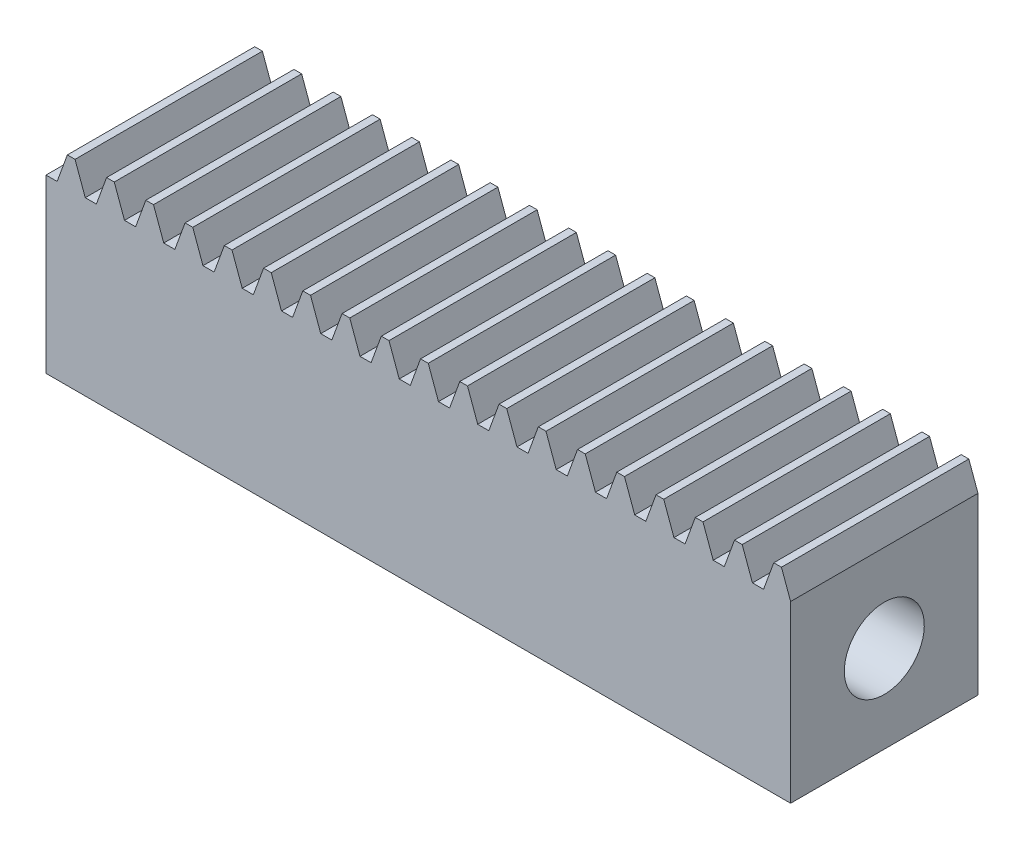
SolidWorks part; units mm, degrees
extrude "Blank" add sketch "BlankSke" against normal blind 15
sketch "BlankSke" plane through (0, 0, 0) normal (0, 0, 1) x (1, 0, 0)
  line L1 (0, 0) -> (100, 0)
  line L2 (0, 0) -> (0, 16)
  line L3 (0, 16) -> (100, 16)
  line L4 (100, 0) -> (100, 16)
  dimension "Length" = 100
ref_plane "Plane1" through (0, 0, 0) normal (0, 0, 1) x (1, 0, 0)
ref_plane "Plane2" through (0, 0, 0) normal (0, 1, 0) x (1, 0, 0)
ref_plane "Plane3" through (0, 0, 0) normal (1, 0, 0) x (0, 0, -1)
sketch "HoldingSke" plane through (0, 0, 0) normal (0, 1, 0) x (1, 0, 0)
  line L0 (0, 0) -> (0.1392, 0.9903)
  line L1 (-15, 0) -> (100, 0) construction
  line L2 (0, 0) -> (-2.1039, 2.3779)
  line L3 (0, 0) -> (-11.863, 4.5341)
  line L4 (0, 0) -> (7.2428, 4.7035)
  line L5 (0, 0) -> (-23.7986, -8.8762)
  line L6 (0, 0) -> (-10.5278, -7.1032)
  line L9 (-71.009, 38.7566) -> (22.9603, 72.9586)
  line L10 (-76.2, 3.3779) -> (-61.2, 3.3779)
  line L11 (0, 0) -> (-15, 0)
  line L12 (-76.2, 101.6) -> (-76.162, 101.6)
  line L13 (24.9733, 27.94) -> (52.9518, 28.4284)
  line L14 (24.9733, 27.94) -> (24.9743, 27.94)
  line L15 (24.9733, 27.94) -> (100.4006, 29.5858)
  circle A0 centre (0, 0) radius 19.05
  circle A1 centre (0, 0) radius 7.5
  circle A2 centre (0, 0) radius 12.7
  dimension "Num_teeth" = 33
  dimension "Width" = 15
  dimension "Length" = 100
  dimension "Pitch_height" = 15
sketch "TooCutSkeIll" plane through (0, 0, 0) normal (0, 0, 1) x (1, 0, 0)
  line L0 (-1.2538, 15.9737) -> (-0.5045, 13.9152)
  line L1 (-0.2687, 13.75) -> (0.2687, 13.75)
  line L2 (0.5045, 13.9152) -> (1.2538, 15.9737)
  line L3 (100, 16) -> (0, 16) construction
  line L4 (0, 0) -> (0, 64.897) construction
  line L5 (-13.208, 15) -> (12.954, 15) construction
  line L6 (0, 0) -> (100, 0) construction
  line L7 (0.8994, 15) -> (0.8994, 48.7463) construction
  line L8 (-0.8994, 15) -> (-0.8994, 48.7463) construction
  line L9 (1.2914, 16) -> (1.2914, 16.0254)
  line L10 (-1.2914, 16) -> (-1.2914, 16.0254)
  line L11 (-1.2914, 16.0254) -> (1.2914, 16.0254)
  arc A0 (0.2687, 13.75) -> (0.5045, 13.9152) centre (0.2687, 14.001) ccw
  arc A1 (-0.5045, 13.9152) -> (-0.2687, 13.75) centre (-0.2687, 14.001) ccw
  arc A2 (1.2914, 16) -> (1.2538, 15.9737) centre (1.2914, 15.96) ccw
  arc A3 (-1.2538, 15.9737) -> (-1.2914, 16) centre (-1.2914, 15.96) ccw
  dimension "Addendum_plus" = 1.0254
  dimension "Pitch_height" = 15
  dimension "Pressure_angle" = 20
  dimension "Gap_width" = 1.7988
  dimension "Dedendum" = 1.25
extrude "ToothCutIll" [suppressed] cut sketch "TooCutSkeIll" against normal through all
sketch "TooCutSkeSim" plane through (0, 0, 0) normal (0, 0, 1) x (1, 0, 0)
  line L0 (0.4444, 13.75) -> (-0.4444, 13.75)
  line L1 (1.2726, 16.0254) -> (0.4444, 13.75)
  line L2 (0, 17.4625) -> (0, 53.467) construction
  line L3 (1.2726, 16.0254) -> (-1.2726, 16.0254)
  line L6 (-1.2726, 16.0254) -> (-0.4444, 13.75)
  line L9 (-0.8994, 15) -> (0.8994, 15) construction
  line L10 (0, 0) -> (100, 0) construction
  line L11 (0.8994, 15) -> (0.8994, 53.467) construction
  line L12 (-0.8994, 15) -> (-0.8994, 53.467) construction
  dimension "Addendum_plus" = 1.0254
  dimension "Pitch_height" = 15
  dimension "Pressure_angle" = 20
  dimension "Gap_width" = 1.7988
  dimension "Dedendum" = 1.25
extrude "ToothCutSim" cut sketch "TooCutSkeSim" against normal through all
pattern_linear "TeethCuts" count 33 spacing 3.1416 along (1, 0, 0) of "ToothCutIll", "ToothCutSim"
sketch "Sketch1" plane through (100, 0, 0) normal (1, 0, 0) x (0, 0, -1)
  line L0 (0, 13.9877) -> (15, 0) construction
  circle A0 centre (7.5, 6.9939) radius 3.2
  dimension "D1" = 6.4
extrude "Cut-Extrude1" cut sketch "Sketch1" against normal blind 50
sketch "Sketch2" plane through (0, 0, 0) normal (0, 0, 1) x (1, 0, 0)
  line L1 (0, 0) -> (40.3963, 0)
  line L2 (0, 0) -> (0, 26.2501)
  line L3 (0, 26.2501) -> (40.3963, 26.2501)
  line L4 (40.3963, 0) -> (40.3963, 26.2501)
extrude "Cut-Extrude2" cut sketch "Sketch2" against normal through all
fillet "Fillet1" [suppressed] radius 8
equation "' \"Module@HoldingSke\" = 6.35"
equation "' \"Num_teeth@HoldingSke\" = 12"
equation "' \"Ap@HoldingSke\" =  20"
equation "' \"Ap@HoldingSke\" = 20"
equation "' \"Width@HoldingSke\" = 0.25 * 25.4"
equation "' \"Show_teeth@HoldingSke\" = 500"
equation "' \"Backlash@HoldingSke\" = 0.009 * 25.4"
equation "' \"Addendum_fac@HoldingSke\" = 1.0"
equation "' \"Dedendum_fac@HoldingSke\" = 1.25"
equation "' \"Dedendum_add@HoldingSke\" = 0.00005 * 25.4"
equation "' \"Clearance_fac@HoldingSke\" = 0.25"
equation "' \"Pitch_height@HoldingSke\" = 1 * 25.4"
equation "' \"Length@HoldingSke\" = 4.71 * 25.4"
equation "\"Pitch@HoldingSke\" = 1 / \"Module@HoldingSke\""
equation "\"MPH@HoldingSke\" = \"Dedendum_fac@HoldingSke\" / \"Pitch@HoldingSke\" + 2 * \"Dedendum_add@HoldingSke\" + 0.002 * 25.4"
equation "\"MPH@HoldingSke\" = ((sgn( \"MPH@HoldingSke\" - \"Pitch_height@HoldingSke\")+1)*( \"MPH@HoldingSke\" - \"Pitch_height@HoldingSke\"))/2 + \"Pitch_height@HoldingSke\""
equation "\"Blank_height@BlankSke\" = \"Pitch_height@HoldingSke\" + \"Addendum_fac@HoldingSke\"  / \"Pitch@HoldingSke\" "
equation "\"Length@BlankSke\" =  \"Length@HoldingSke\""
equation "\"Face_width@Blank\" = \"Width@HoldingSke\""
equation "\"Pressure_angle@TooCutSkeIll\" = \"Ap@HoldingSke\""
equation "\"Addendum_plus@TooCutSkeIll\" =  \"Addendum_fac@HoldingSke\"  / \"Pitch@HoldingSke\" + 0.001 *25.4"
equation "\"Dedendum@TooCutSkeIll\" = \"Dedendum_fac@HoldingSke\"  / \"Pitch@HoldingSke\""
equation "\"Pitch_height@TooCutSkeIll\" =  \"MPH@HoldingSke\""
equation "\"Gap_width@TooCutSkeIll\" = 3.14159265 / 2 / \"Pitch@HoldingSke\" + 6 * \"Backlash@HoldingSke\""
equation "\"Pressure_angle@TooCutSkeSim\" = \"Ap@HoldingSke\""
equation "\"Addendum_plus@TooCutSkeSim\" =  \"Addendum_fac@HoldingSke\"  / \"Pitch@HoldingSke\" + 0.001 * 25.4"
equation "\"Dedendum@TooCutSkeSim\" = \"Dedendum_fac@HoldingSke\"  / \"Pitch@HoldingSke\""
equation "\"Pitch_height@TooCutSkeSim\" =  \"MPH@HoldingSke\""
equation "\"Gap_width@TooCutSkeSim\" = 3.14159265 / 2 / \"Pitch@HoldingSke\" + 6 * \"Backlash@HoldingSke\""
equation "\"Root_fillet@TooCutSkeIll\" = \"Clearance_fac@HoldingSke\" / \"Pitch@HoldingSke\" + \"Dedendum_add@HoldingSke\""
equation "\"Break_rad@TooCutSkeIll\" = 0.02 / \"Pitch@HoldingSke\" * 2"
equation "\"Linear_pitch@TeethCuts\" = 3.14159265 / \"Pitch@HoldingSke\""
equation "\"Num_teeth@HoldingSke\" = int( ( \"Length@HoldingSke\" + 0 ) / (3.14159265 / \"Pitch@HoldingSke\")) + 0.9999  + 1"
equation " \"Num_teeth@TeethCuts\" = int( \"Show_teeth@HoldingSke\" ) + 1"
equation " \"Num_teeth@TeethCuts\" = ((sgn( \"Num_teeth@TeethCuts\" - \"Num_teeth@HoldingSke\" )-1)*( \"Num_teeth@TeethCuts\" - \"Num_teeth@HoldingSke\" ))/-2+ \"Num_teeth@HoldingSke\""
equation " \"Num_teeth@TeethCuts\" = ((sgn( \"Num_teeth@TeethCuts\" - 2.0)+1)*( \"Num_teeth@TeethCuts\" - 2.0))/2 +2.0"
